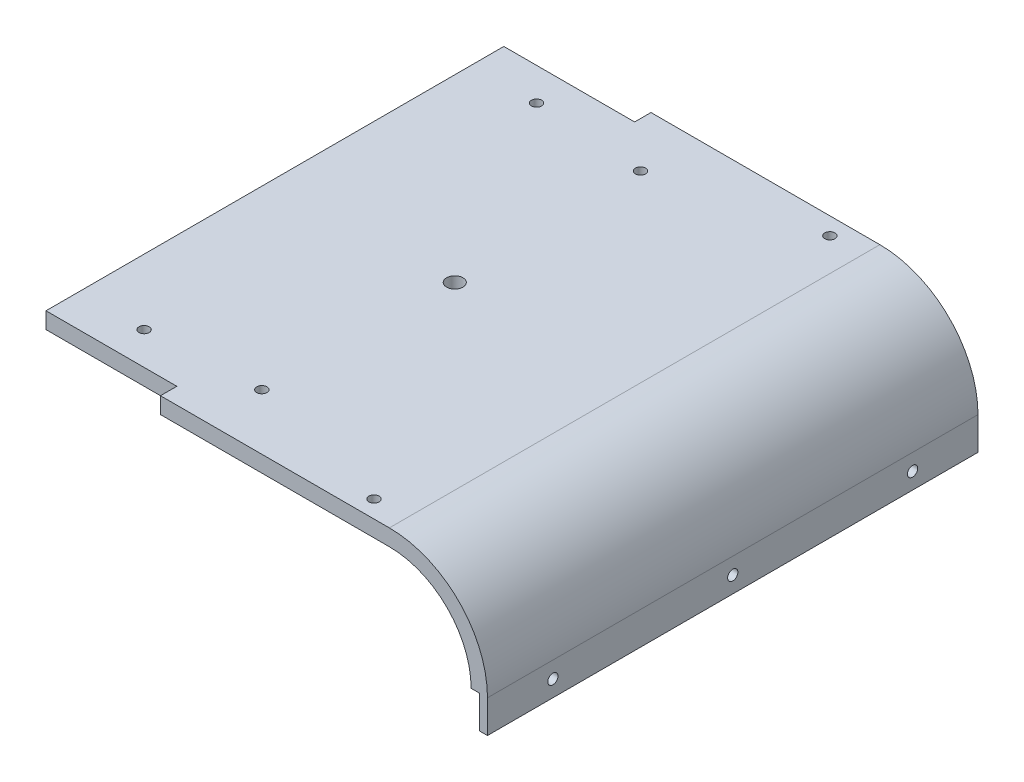
SolidWorks part; units mm, degrees
ref_plane "Front Plane" through (0, 0, 0) normal (0, 0, 1) x (1, 0, 0)
ref_plane "Top Plane" through (0, 0, 0) normal (0, 1, 0) x (1, 0, 0)
ref_plane "Right Plane" through (0, 0, 0) normal (1, 0, 0) x (0, 0, -1)
sketch "Sketch1" plane through (0, 0, 0) normal (0, 0, 1) x (1, 0, 0)
  line L0 (-139.7, 0) -> (139.7, 0)
  line L1 (139.7, 0) -> (139.7, -152.4) construction
  line L2 (139.7, -76.2) -> (215.9, -76.2) construction
  line L3 (-139.7, -12.7) -> (139.7, -12.7)
  line L4 (-139.7, 0) -> (-139.7, -12.7)
  line L5 (215.9, -76.2) -> (203.2, -76.2)
  circle A0 centre (139.7, -76.2) radius 76.2 construction
  arc A1 (139.7, 0) -> (215.9, -76.2) centre (139.7, -76.2) cw
  arc A2 (139.7, -12.7) -> (203.2, -76.2) centre (139.7, -76.2) cw
  point P4 (0, 0)
  dimension "D1" = 152.4
  dimension "D2" = 355.6
  dimension "D3" = 12.7
extrude "Boss-Extrude1" add sketch "Sketch1" along normal blind 190.5 and the other way blind 190.5
sketch "Sketch2" plane through (0, -76.2, 0) normal (0, -1, 0) x (1, 0, 0)
  line L0 (203.2, 190.5) -> (215.9, 190.5) construction
  line L1 (209.55, 190.5) -> (215.9, 190.5)
  line L2 (209.55, 190.5) -> (209.55, -190.5)
  line L3 (209.55, -190.5) -> (215.9, -190.5)
  line L4 (215.9, 190.5) -> (215.9, -190.5)
extrude "Boss-Extrude2" add sketch "Sketch2" along normal blind 25.4
sketch "Sketch3" plane through (215.9, 0, 0) normal (1, 0, 0) x (0, 0, -1)
  line L0 (-190.5, -88.9) -> (190.5, -88.9) construction
  line L1 (-190.5, -101.6) -> (-190.5, -76.2) construction
  line L2 (190.5, -101.6) -> (190.5, -76.2) construction
  line L3 (0, -76.2) -> (0, -101.6) construction
  line L4 (190.5, -76.2) -> (-190.5, -76.2) construction
  line L5 (190.5, -101.6) -> (-190.5, -101.6) construction
  line L6 (139.7, -76.2) -> (139.7, -101.6) construction
  line L7 (-139.7, -76.2) -> (-139.7, -101.6) construction
  circle A0 centre (-139.7, -88.9) radius 3.9687
  circle A1 centre (0, -88.9) radius 3.9687
  circle A2 centre (139.7, -88.9) radius 3.9687
  dimension "D3" = 7.9375
  dimension "D1" = 139.7
  dimension "D2" = 139.7
extrude "Cut-Extrude1" cut sketch "Sketch3" against normal blind 25.4
sketch "Sketch4" plane through (0, 0, 0) normal (0, 1, 0) x (1, 0, 0)
  circle A0 centre (0, 0) radius 6.35
  dimension "D1" = 12.7
extrude "Cut-Extrude2" cut sketch "Sketch4" against normal blind 17.78
sketch "Sketch5" plane through (0, 0, 0) normal (0, 1, 0) x (1, 0, 0)
  line L0 (139.7, 0) -> (114.3, 0) construction
  line L1 (139.7, 190.5) -> (139.7, -190.5) construction
  line L2 (-139.7, 190.5) -> (-139.7, -190.5) construction
  line L3 (-2.794, 0) -> (-2.794, -147.066) construction
  line L4 (114.3, 177.8) -> (114.3, -177.8) construction
  line L5 (-114.3, -177.8) -> (-114.3, 177.8) construction
  line L6 (139.7, -190.5) -> (-139.7, -190.5) construction
  line L7 (-114.3, 0) -> (-139.7, 0) construction
  line L8 (-114.3, 0) -> (0, 0) construction
  line L9 (0, 0) -> (114.3, 0) construction
  line L12 (-114.3, -177.8) -> (-139.7, -177.8)
  line L13 (-139.7, -177.8) -> (-139.7, -190.5)
  line L14 (-139.7, -190.5) -> (-38.1, -190.5)
  line L15 (-38.1, -190.5) -> (-38.1, -177.8)
  line L16 (-38.1, -177.8) -> (-114.3, -177.8)
  line L27 (-38.1, 190.5) -> (-38.1, 177.8)
  line L28 (-139.7, 190.5) -> (-38.1, 190.5)
  line L29 (-139.7, 177.8) -> (-139.7, 190.5)
  line L30 (-114.3, 177.8) -> (-139.7, 177.8)
  line L31 (-38.1, 177.8) -> (-114.3, 177.8)
  line L32 (139.7, 190.5) -> (-139.7, 190.5) construction
  line L33 (-2.794, 0) -> (-2.794, 147.066) construction
  line L34 (-88.9, 152.4) -> (-88.9, -152.4) construction
  circle A3 centre (114.3, -177.038) radius 3.937
  circle A4 centre (114.3, 177.038) radius 3.937
  circle A5 centre (-2.794, -147.066) radius 3.937
  circle A6 centre (-2.794, 147.066) radius 3.937
  circle A7 centre (-88.9, -152.4) radius 3.937
  circle A8 centre (-88.9, 152.4) radius 3.937
  point P11 (0, 0)
  point P15 (114.3, 0)
  point P18 (-114.3, 0)
  dimension "D3" = 13.462
  dimension "D2" = 7.874
  dimension "D8" = 7.874
  dimension "D12" = 7.874
  dimension "D13" = 50.8
  dimension "D1" = 12.7
  dimension "D4" = 101.6
  dimension "D5" = 13.462
  dimension "D6" = 114.3
  dimension "D7" = 43.434
  dimension "D9" = 136.906
  dimension "D10" = 38.1
  dimension "D11" = 38.1
extrude "Cut-Extrude3" cut sketch "Sketch5" against normal through all
